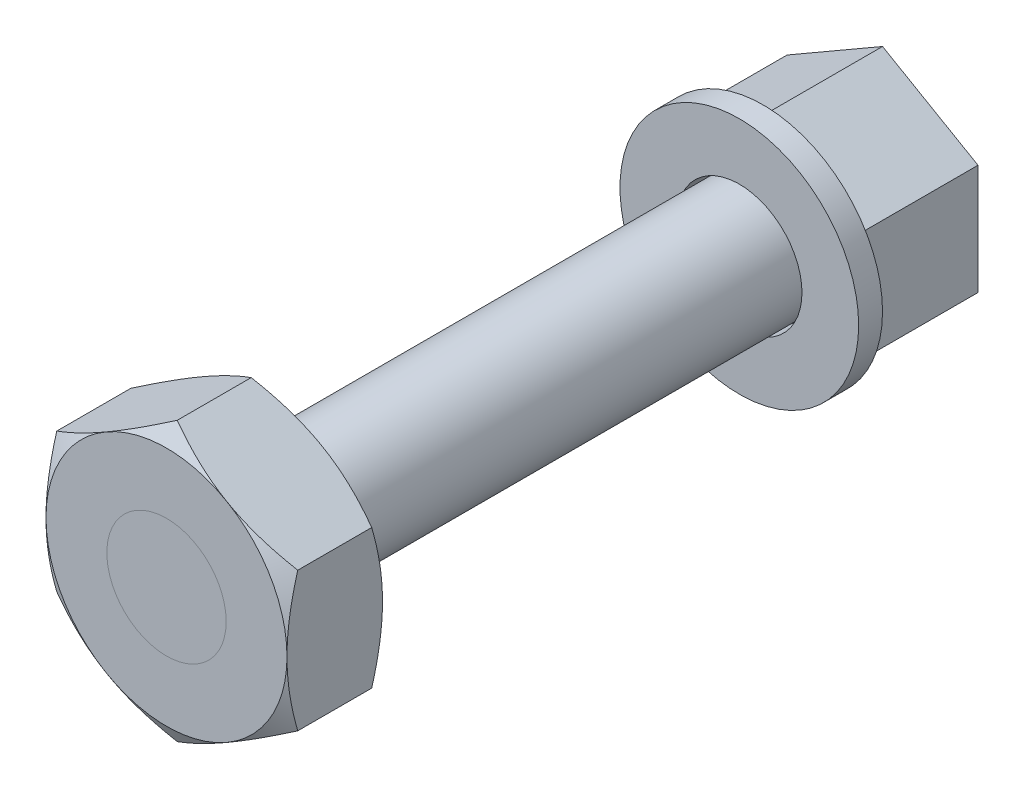
SolidWorks part; units mm, degrees
other "Vite"
other "Rosetta"
other "Dado"
ref_plane "Piano frontale" through (0, 0, 0) normal (0, 0, 1) x (1, 0, 0)
ref_plane "Piano superiore" through (0, 0, 0) normal (0, 1, 0) x (1, 0, 0)
ref_plane "Piano destro" through (0, 0, 0) normal (1, 0, 0) x (0, 0, -1)
sketch "Sketch1" plane through (0, 0, 0) normal (0, 0, 1) x (1, 0, 0)
  line L1 (-3.1632, 12.1549) -> (-11.1632, 16.7737)
  line L2 (-11.1632, 16.7737) -> (-19.1632, 12.1549)
  line L3 (-19.1632, 12.1549) -> (-19.1632, 2.9173)
  line L4 (-19.1632, 2.9173) -> (-11.1632, -1.7015)
  line L5 (-11.1632, -1.7015) -> (-3.1632, 2.9173)
  line L6 (-3.1632, 2.9173) -> (-3.1632, 12.1549)
  circle A0 centre (-11.1632, 7.5361) radius 8 construction
  circle A1 centre (-11.1632, 7.5361) radius 5
  dimension "D1" = 10
  dimension "D2" = 16
extrude "Boss-Extrude1" add sketch "Sketch1" along normal blind 10 contours A1 | L5 L6 L1 L2 L3 L4 A1 region at (-3.4076, 7.5361, 0) region at (-11.1632, 7.5361, 0)
extrude "Boss-Extrude2" add sketch "Sketch1<3>" along normal blind 50 from surface contours A1 region at (-11.1632, 7.5361, 0) starting at face at (-11.1632, 7.5361, 10)
sketch "Sketch1<3>" plane through (0, 0, 0) normal (0, 0, 1) x (1, 0, 0) same geometry as "Sketch1"
sketch "Sketch3" plane through (0, 0, 0) normal (0, 0, 1) x (1, 0, 0)
  circle A0 centre (-11.1632, 7.5361) radius 10
  circle A1 centre (-11.1632, 7.5361) radius 5 construction
  circle A2 centre (-11.1632, 7.5361) radius 5.25
  dimension "D1" = 20
  dimension "D2" = 10.5
extrude "Boss-Extrude3" add sketch "Sketch3" along normal blind 2 from surface separate body starting at face at (-6.1632, 7.5361, 10)
sketch "Sketch4" plane through (0, 0, 60) normal (0, 0, 1) x (1, 0, 0)
  line L7 (-19.1632, 12.1549) -> (-19.1632, 2.9173) construction
  line L8 (-11.1632, -4.1236) -> (-1.0656, 1.7062)
  line L9 (-1.0656, 1.7062) -> (-1.0656, 13.366)
  line L10 (-1.0656, 13.366) -> (-11.1632, 19.1958)
  line L11 (-11.1632, 19.1958) -> (-21.2608, 13.366)
  line L12 (-21.2608, 13.366) -> (-21.2608, 1.7062)
  line L13 (-21.2608, 1.7062) -> (-11.1632, -4.1236)
  circle A3 centre (-11.1632, 7.5361) radius 10.0976 construction
  circle A4 centre (-11.1632, 7.5361) radius 5 construction
  circle A5 centre (-11.1632, 7.5361) radius 5
extrude "Boss-Extrude4" add sketch "Sketch4" against normal blind 8 separate body
ref_plane "Plane1" through (0, 7.5361, 0) normal (0, -1, 0) x (-1, 0, 0)
sketch "Sketch5" plane through (0, 7.5361, 0) normal (0, -1, 0) x (-1, 0, 0)
  line L0 (28.189, -56) -> (14.3326, -64)
  line L1 (14.3326, -64) -> (14.3326, -68.5)
  line L2 (14.3326, -68.5) -> (39.3326, -68.5)
  line L3 (39.3326, -68.5) -> (39.3326, -43.5)
  line L4 (39.3326, -43.5) -> (14.3326, -43.5)
  line L5 (14.3326, -43.5) -> (14.3326, -48)
  line L6 (14.3326, -48) -> (28.189, -56)
  line L7 (14.3326, -64) -> (20.4964, -64) construction
  line L8 (14.3326, -48) -> (20.7305, -48) construction
  point P7 (21.2608, -60)
  point P10 (21.2608, -52)
  dimension "D1" = 30
  dimension "D2" = 30
  dimension "D3" = 25
  dimension "D4" = 25
ref_plane "Plane2" through (-11.1632, 0, 0) normal (1, 0, 0) x (0, 0, -1)
ref_axis "Axis1" through (-11.1632, 7.5361, 101.6) along (0, 0, 1)
revolve "Cut-Revolve1" cut sketch "Sketch5" angle 360 about axis through (-11.1632, 7.5361, 101.6) along (0, 0, 1)
